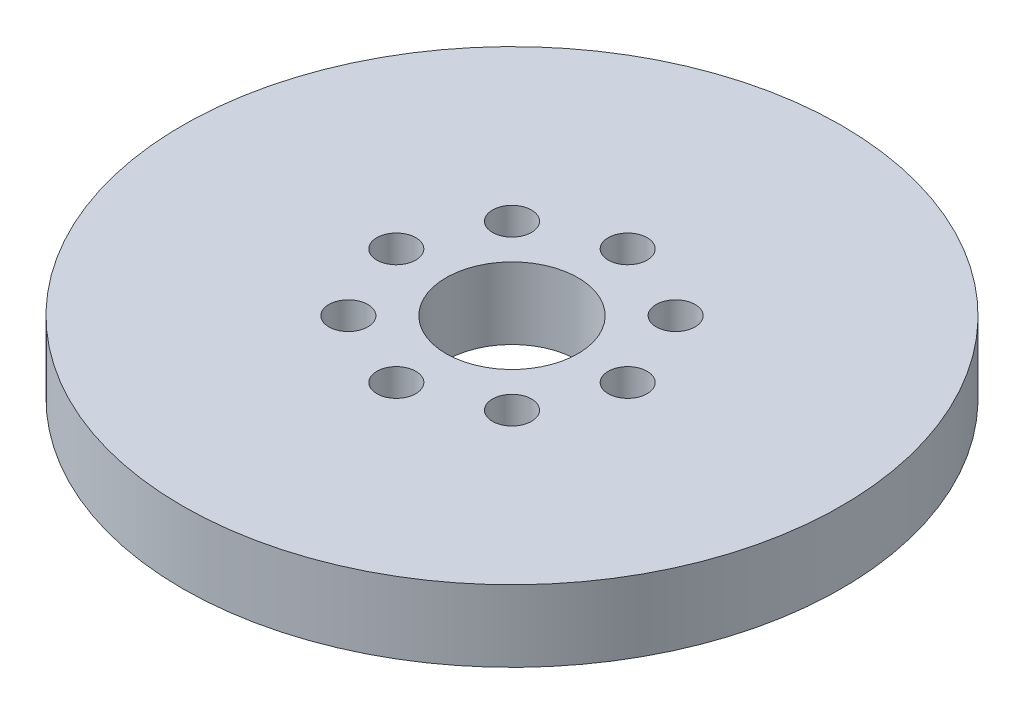
SolidWorks part; units mm, degrees
ref_plane "Front Plane" through (0, 0, 0) normal (0, 0, 1) x (1, 0, 0)
ref_plane "Top Plane" through (0, 0, 0) normal (0, 1, 0) x (1, 0, 0)
ref_plane "Right Plane" through (0, 0, 0) normal (1, 0, 0) x (0, 0, -1)
sketch "Sketch1" plane through (0, 0, 0) normal (0, 1, 0) x (1, 0, 0)
  circle A0 centre (0, 0) radius 87.5
  dimension "FLANGE_OD" = 175
extrude "Boss-Extrude1" add sketch "Sketch1" along normal blind 19
sketch "Sketch2" plane through (0, 0, 0) normal (0, 1, 0) x (1, 0, 0)
  circle A0 centre (0, 0) radius 17.5
  dimension "BORE_D" = 35
extrude "Cut-Extrude1" cut sketch "Sketch2" along normal through all
sketch "Sketch3" plane through (0, 19, 0) normal (0, 1, 0) x (1, 0, 0)
  circle A0 centre (0, 0) radius 30.7195 construction
  circle A1 centre (-30.7195, 0) radius 5.171
  dimension "BOLT_D" = 10.342
  dimension "BOLT_PCD" = 61.4391
extrude "Cut-Extrude2" cut sketch "Sketch3" against normal blind 13.9489
pattern_circular "CirPattern1" count 8 over 360 about axis through (0, 0, 0) along (0, 1, 0) of "Cut-Extrude2"
